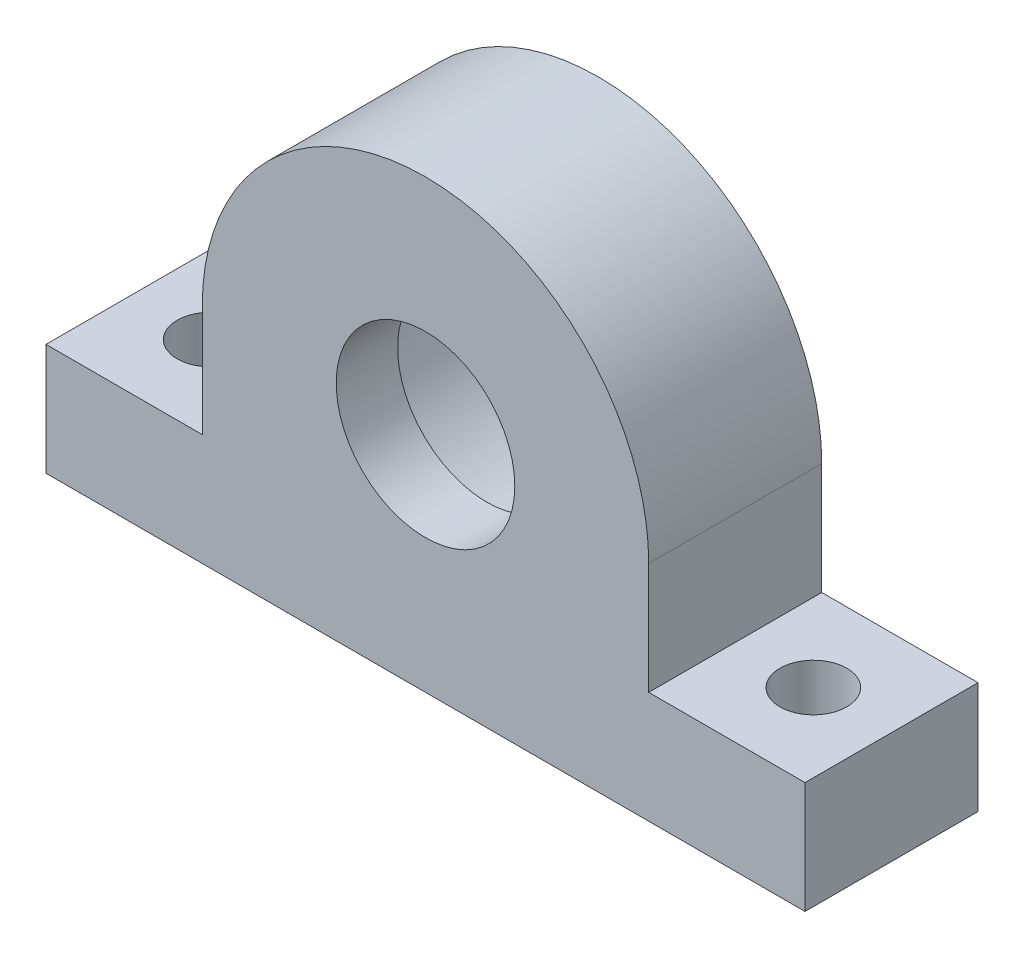
SolidWorks part; units mm, degrees
ref_plane "Front Plane" through (0, 0, 0) normal (0, 0, 1) x (1, 0, 0)
ref_plane "Top Plane" through (0, 0, 0) normal (0, 1, 0) x (1, 0, 0)
ref_plane "Right Plane" through (0, 0, 0) normal (1, 0, 0) x (0, 0, -1)
sketch "Sketch1" plane through (0, 0, 0) normal (0, 0, 1) x (1, 0, 0)
  line L0 (-34, 0) -> (34, 0)
  line L1 (34, 0) -> (34, 10)
  line L2 (34, 10) -> (20, 10)
  line L3 (20, 10) -> (20, 20)
  line L4 (0, -55) -> (0, 55) construction
  line L5 (-20, 10) -> (-20, 20)
  line L6 (-34, 10) -> (-20, 10)
  line L7 (-34, 0) -> (-34, 10)
  arc A0 (20, 20) -> (-20, 20) centre (0, 20) ccw
  circle A1 centre (0, 20) radius 13.1
  point P16 (0, 0)
  dimension "D2" = 20
  dimension "D1" = 26.2
  dimension "10" = 10
  dimension "D3" = 34
  dimension "D4" = 20
extrude "Boss-Extrude1" add sketch "Sketch1" along normal blind 10
sketch "Sketch2" plane through (0, 0, 10) normal (0, 0, 1) x (1, 0, 0)
  line L7 (34, 0) -> (34, 10)
  line L8 (34, 10) -> (20, 10)
  line L9 (20, 10) -> (20, 20)
  line L10 (-20, 20) -> (-20, 10)
  line L11 (-20, 10) -> (-34, 10)
  line L12 (-34, 10) -> (-34, 0)
  line L13 (-34, 0) -> (34, 0)
  line L14 (34, 0) -> (34, 10)
  line L15 (34, 10) -> (20, 10)
  line L16 (20, 10) -> (20, 20)
  line L17 (-20, 20) -> (-20, 10)
  line L18 (-20, 10) -> (-34, 10)
  line L19 (-34, 10) -> (-34, 0)
  line L20 (-34, 0) -> (34, 0)
  circle A0 centre (0, 20) radius 8
  arc A1 (20, 20) -> (-20, 20) centre (0, 20) ccw
  arc A2 (20, 20) -> (-20, 20) centre (0, 20) ccw
  dimension "D2" = 16
  dimension "D1" = 0
extrude "Boss-Extrude2" add sketch "Sketch2" along normal blind 5.5
sketch "Sketch3" plane through (0, 10, 0) normal (0, 1, 0) x (1, 0, 0)
  line L0 (-20, -15.5) -> (-34, 0) construction
  line L1 (20, -15.5) -> (34, 0) construction
  circle A0 centre (27, -7.75) radius 3
  circle A1 centre (-27, -7.75) radius 3
  point P12 (0, 0)
  point P13 (-27, -7.75)
  point P14 (0, 0)
  point P15 (27, -7.75)
  dimension "D1" = 6
  dimension "D2" = 6
extrude "Cut-Extrude1" cut sketch "Sketch3" against normal through all
